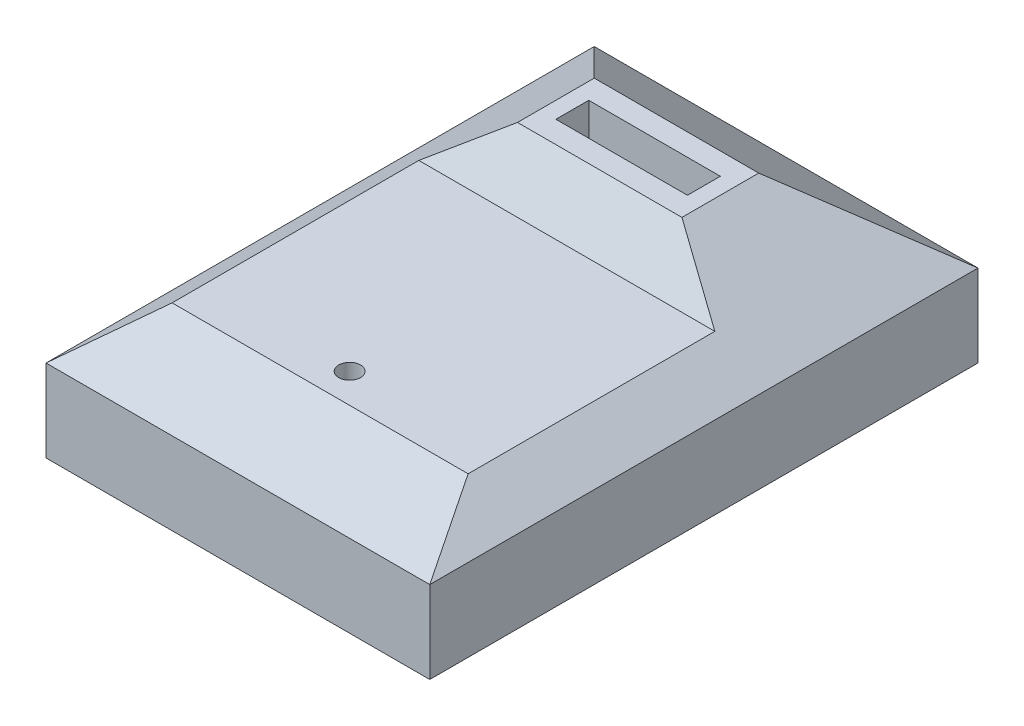
SolidWorks part; units mm, degrees
ref_plane "Ebene vorne" through (0, 0, 0) normal (0, 0, 1) x (1, 0, 0)
ref_plane "Ebene oben" through (0, 0, 0) normal (0, 1, 0) x (1, 0, 0)
ref_plane "Ebene rechts" through (0, 0, 0) normal (1, 0, 0) x (0, 0, -1)
sketch "Skizze1" plane through (0, 0, 0) normal (0, 0, 1) x (1, 0, 0)
  line L1 (0, 0) -> (70, 0)
  line L2 (0, 0) -> (0, 30)
  line L3 (0, 30) -> (70, 30)
  line L4 (70, 0) -> (70, 30)
  dimension "D1" = 70
  dimension "D2" = 30
extrude "Aufsatz-Linear austragen1" add sketch "Skizze1" along normal blind 100
sketch "Skizze4" plane through (70, 0, 0) normal (1, 0, 0) x (0, 0, -1)
  line L0 (0, 15) -> (-20, 30)
  line L1 (0, 0) -> (0, 30) construction
  line L2 (-100, 30) -> (0, 30) construction
  line L3 (-20, 30) -> (0, 30)
  line L4 (0, 30) -> (0, 15)
  dimension "D1" = 20
extrude "Schnitt-Linear austragen2" cut sketch "Skizze4" against normal through all
sketch "Skizze5" plane through (0, 0, 100) normal (0, 0, 1) x (1, 0, 0)
  line L0 (0, 30) -> (20, 30)
  line L1 (70, 30) -> (0, 30) construction
  line L2 (20, 30) -> (0, 15)
  line L3 (0, 30) -> (0, 0) construction
  line L4 (0, 15) -> (0, 30)
  line L5 (70, 30) -> (50, 30)
  line L6 (50, 30) -> (70, 15)
  line L7 (70, 0) -> (70, 30) construction
  line L8 (70, 15) -> (70, 30)
  dimension "D1" = 20
extrude "Schnitt-Linear austragen3" cut sketch "Skizze5" against normal blind 100
sketch "Skizze8" plane through (70, 0, 0) normal (1, 0, 0) x (0, 0, -1)
  line L0 (-100, 30) -> (-100, 15)
  line L1 (-100, 15) -> (-85, 21)
  line L2 (-85, 21) -> (-40, 21)
  line L3 (-40, 21) -> (-34, 30)
  line L4 (-20, 30) -> (-100, 30) construction
  line L5 (-34, 30) -> (-100, 30)
  dimension "D1" = 45
  dimension "D2" = 15
  dimension "D3" = 9
  dimension "D4" = 6
extrude "Schnitt-Linear austragen4" cut sketch "Skizze8" against normal through all
ref_axis "Achse1" through (35, 15, 0) along (0, 0, 1)
shell "Wandung1" thickness 2 removed face at (35, 0, 50)
sketch "Skizze10" plane through (0, 19, 0) normal (0, -1, 0) x (1, 0, 0)
  line L0 (70, 100) -> (70, 0) construction
  line L1 (8.6667, 84.6148) -> (61.3333, 84.6148) construction
  circle A0 centre (35, 79.6148) radius 3
  dimension "D1" = 35
  dimension "D3" = 6
  dimension "D2" = 5
extrude "Aufsatz-Linear austragen2" add sketch "Skizze10" along normal blind 2
sketch "Skizze12" plane through (0, 17, 0) normal (0, -1, 0) x (1, 0, 0)
  circle A0 centre (35, 79.6148) radius 2
extrude "Aufsatz-Linear austragen3" add sketch "Skizze12" along normal blind 5
sketch "Skizze13" plane through (0, 12, 0) normal (0, -1, 0) x (1, 0, 0)
  circle A0 centre (35, 79.6148) radius 1.5
extrude "Schnitt-Linear austragen5" cut sketch "Skizze13" against normal through all
sketch "Skizze15" plane through (0, 21, 0) normal (0, 1, 0) x (1, 0, 0)
  circle A0 centre (35, -79.6148) radius 2
extrude "Schnitt-Linear austragen6" cut sketch "Skizze15" against normal blind 3
sketch "Skizze26" plane through (0, 30, 0) normal (0, 1, 0) x (1, 0, 0)
  line L0 (35, 0) -> (35, -100) construction
  line L1 (22, -31) -> (48, -31)
  line L2 (22, -31) -> (22, -23)
  line L3 (22, -23) -> (48, -23)
  line L4 (48, -31) -> (48, -23)
  line L5 (22, -31) -> (48, -23) construction
  line L6 (22, -23) -> (48, -31) construction
  line L7 (20, -34) -> (50, -34) construction
  point P0 (35, -27)
  dimension "D1" = 26
  dimension "D2" = 8
  dimension "D3" = 3
extrude "Aufsatz-Linear austragen4" add sketch "Skizze26" against normal blind 30
sketch "Skizze27" plane through (0, 30, 0) normal (0, 1, 0) x (1, 0, 0)
  line L0 (35, 0) -> (35, -100) construction
  line L1 (23, -30) -> (47, -30)
  line L2 (23, -30) -> (23, -24)
  line L3 (23, -24) -> (47, -24)
  line L4 (47, -30) -> (47, -24)
  line L5 (23, -30) -> (47, -24) construction
  line L6 (23, -24) -> (47, -30) construction
  line L7 (20, -34) -> (50, -34) construction
  point P0 (35, -27)
  dimension "D1" = 4
  dimension "D2" = 6
  dimension "D3" = 24
extrude "Schnitt-Linear austragen8" cut sketch "Skizze27" against normal blind 28
sketch "Skizze28" plane through (0, 0, 0) normal (0, -1, 0) x (1, 0, 0)
  line L0 (48, 31) -> (22, 31) construction
  line L1 (46, 29) -> (37, 29)
  line L2 (46, 29) -> (46, 25)
  line L3 (46, 25) -> (37, 25)
  line L4 (37, 29) -> (37, 25)
  line L5 (48, 23) -> (22, 23) construction
  line L6 (48, 31) -> (48, 23) construction
  dimension "D1" = 2
  dimension "D2" = 2
  dimension "D3" = 2
  dimension "D4" = 9
extrude "Schnitt-Linear austragen9" cut sketch "Skizze28" against normal up to next
